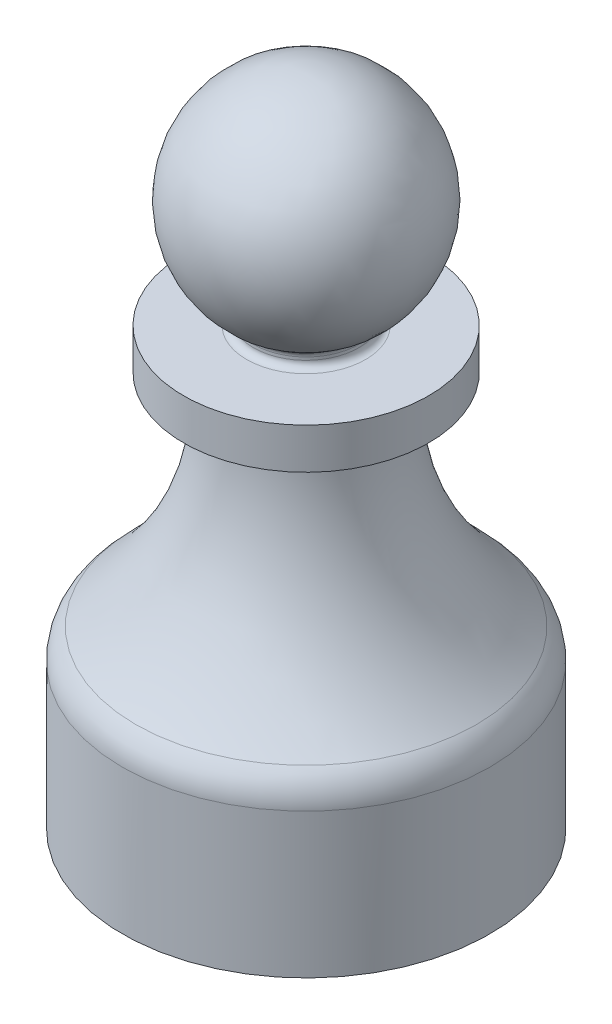
SolidWorks part; units mm, degrees
ref_plane "Front Plane" through (0, 0, 0) normal (0, 0, 1) x (1, 0, 0)
ref_plane "Top Plane" through (0, 0, 0) normal (0, 1, 0) x (1, 0, 0)
ref_plane "Right Plane" through (0, 0, 0) normal (1, 0, 0) x (0, 0, -1)
sketch "Sketch1" plane through (0, 0, 0) normal (0, 0, 1) x (1, 0, 0)
  line L0 (0, 0) -> (13.5, 0)
  line L1 (0, 0) -> (0, 34.7839)
  line L2 (13.5, 0) -> (13.5, 12)
  line L3 (6, 29) -> (9, 29)
  line L4 (9, 29) -> (9, 32)
  line L5 (9, 32) -> (3.873, 32)
  line L6 (0, 34.7839) -> (0, 40)
  line L7 (3.873, 32) -> (3.873, 33)
  line L8 (0, 37) -> (0, 48)
  line L9 (0, 32) -> (3.9543, 27.649)
  line L10 (9.5, 0) -> (9.5, 13.0457)
  line L11 (9.5, 0) -> (9.5, 12) construction
  arc A1 (3.873, 33) -> (0, 48) centre (0, 40) ccw
  arc A2 (13.5, 12) -> (6, 29) centre (25.9543, 27.649) cw
  arc A3 (9.5, 13.0457) -> (3.9543, 27.649) centre (25.9543, 27.649) cw
  arc A4 (12.2546, 10.4351) -> (4.0046, 29.1351) centre (25.9543, 27.649) cw construction
  dimension "D6" = 16
  dimension "D8" = 20
  dimension "D1" = 13.5
  dimension "D2" = 12
  dimension "D3" = 17
  dimension "D4" = 9
  dimension "D5" = 3
  dimension "D7" = 1
  dimension "D9" = 9
  dimension "D10" = 2
  dimension "D11" = 4
  dimension "D16" = 6
revolve "Revolve1" add sketch "Sketch1" angle 360 about L8 region at (9.9986, 6.5228, 0)
chamfer "Chamfer1" distance 2 angle 30 1 edges at (0, 29, -6) first distance on face at (0, 29, -9)
fillet "Fillet1" radius 3 1 edges at (0, 12, -13.5)
fillet "Fillet2" radius 0.5 2 edges at (0, 33, -3.873) (0, 32, -3.873)
